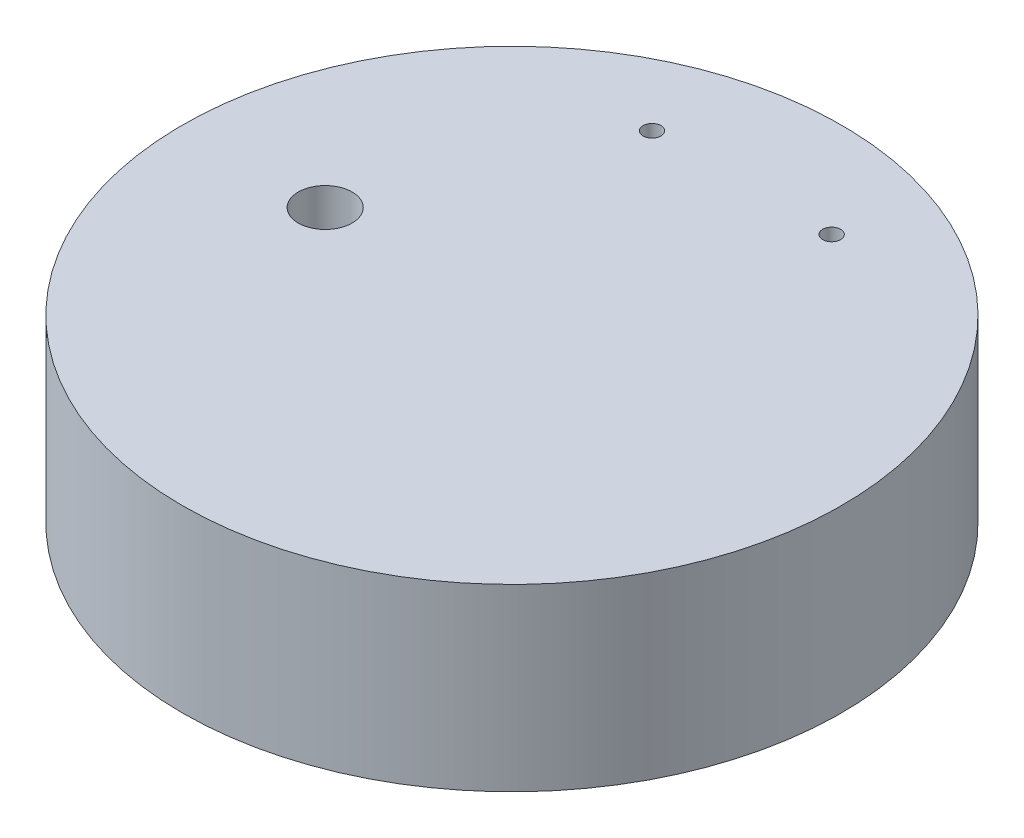
SolidWorks part; units mm, degrees
ref_plane "Front Plane" through (0, 0, 0) normal (0, 0, 1) x (1, 0, 0)
ref_plane "Top Plane" through (0, 0, 0) normal (0, 1, 0) x (1, 0, 0)
ref_plane "Right Plane" through (0, 0, 0) normal (1, 0, 0) x (0, 0, -1)
sketch "Sketch1" plane through (0, 0, 0) normal (0, 1, 0) x (1, 0, 0)
  circle A0 centre (0, 0) radius 46.609
  dimension "D1" = 93.218
extrude "Boss-Extrude1" add sketch "Sketch1" along normal blind 25.4
sketch "Sketch2" plane through (0, 25.4, 0) normal (0, 1, 0) x (1, 0, 0)
  circle A0 centre (0, 32.512) radius 4.9824
  circle A1 centre (12.7, 32.512) radius 1.27
  circle A2 centre (-12.7, 32.512) radius 1.27
  dimension "D4" = 2.54
  dimension "D5" = 2.54
  dimension "D1" = 32.512
  dimension "D2" = 0
  dimension "D3" = 0
  dimension "D6" = 12.7
  dimension "D7" = 12.7
extrude "Cut-Extrude1" cut sketch "Sketch2" against normal blind 25.4 contours A1 | A2 region at (12.7, 25.4, -32.512) region at (-12.7, 25.4, -32.512)
sketch "Sketch3" plane through (0, 25.4, 0) normal (0, 1, 0) x (1, 0, 0)
  circle A0 centre (-26.41, 0) radius 3.81
  dimension "D1" = 7.62
extrude "Cut-Extrude2" cut sketch "Sketch3" against normal up to surface (25.4 mm away) up to face at (12.7, 0, -31.242)
